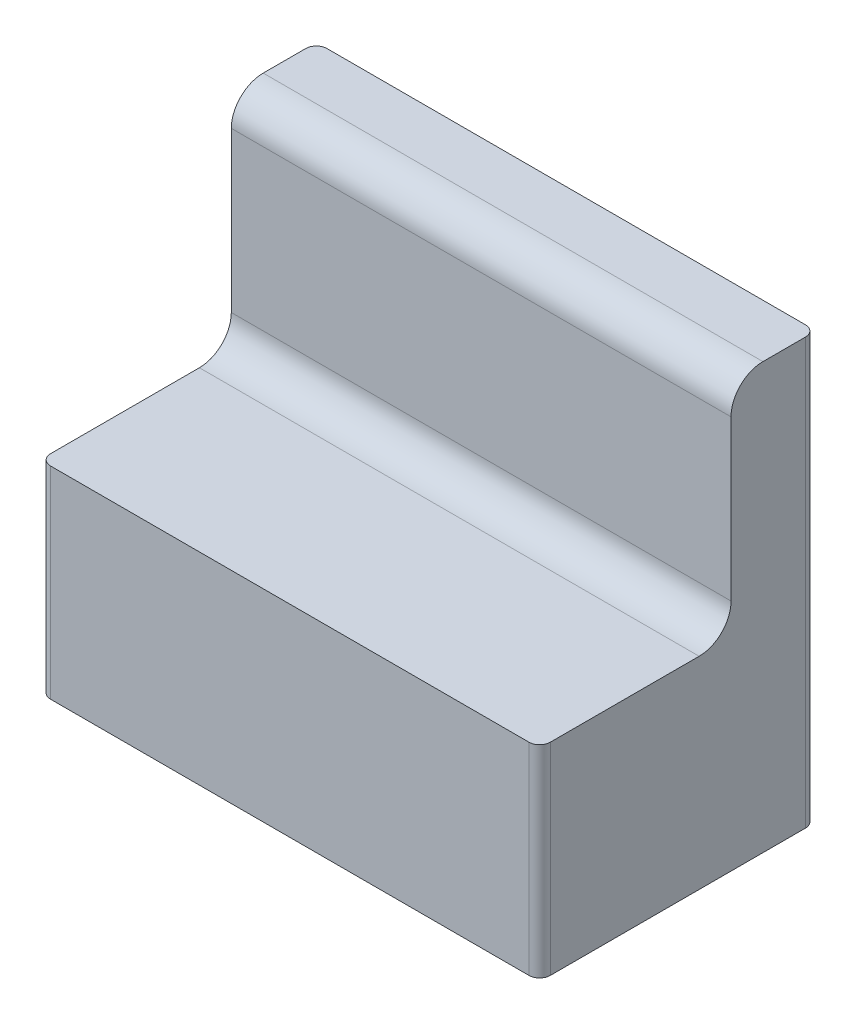
SolidWorks part; units mm, degrees
material "K110"
ref_plane "Front Plane" through (0, 0, 0) normal (0, 0, 1) x (1, 0, 0)
ref_plane "Top Plane" through (0, 0, 0) normal (0, 1, 0) x (1, 0, 0)
ref_plane "Right Plane" through (0, 0, 0) normal (1, 0, 0) x (0, 0, -1)
sketch "Sketch1" plane through (0, 0, 0) normal (0, 1, 0) x (1, 0, 0)
  line L1 (-23.5, -13) -> (23.5, -13)
  line L2 (-23.5, -13) -> (-23.5, 13)
  line L3 (-23.5, 13) -> (23.5, 13)
  line L4 (23.5, -13) -> (23.5, 13)
  line L5 (-23.5, -13) -> (23.5, 13) construction
  line L6 (-23.5, 13) -> (23.5, -13) construction
  point P0 (0, 0)
  dimension "D1" = 26
  dimension "D2" = 47
extrude "Boss-Extrude1" add sketch "Sketch1" against normal blind 40
sketch "Sketch2" plane through (23.5, 0, 0) normal (1, 0, 0) x (0, 0, -1)
  line L0 (13, -40) -> (13, 0) construction
  line L1 (-13, 0) -> (5, 0)
  line L2 (-13, 0) -> (-13, -21)
  line L3 (-13, -21) -> (5, -21)
  line L4 (5, 0) -> (5, -21)
  dimension "D1" = 8
  dimension "D2" = 21
extrude "Cut-Extrude1" cut sketch "Sketch2" against normal up to next
fillet "Fillet1" radius 3 2 edges at (0, 0, -5) (0, -21, -5)
hole_wizard "M6 Tapped Hole1" positions "Sketch6" profile "Sketch4" tap size "M6" standard "ISO"
sketch "Sketch6" plane through (0, -40, 0) normal (0, -1, 0) x (-1, 0, 0)
  line L0 (-23.5, -13) -> (-23.5, 13) construction
  line L1 (23.5, 13) -> (23.5, -13) construction
  point P0 (-15.5, 0)
  point P2 (15.5, 0)
  point P5 (0, 0)
  dimension "D1" = 8
  dimension "D2" = 8
sketch "Sketch4" plane through (15.5, -40, 0) normal (1, 0, 0) x (0, 0, -1)
  line L0 (0, 0) -> (0, 16.5022)
  line L1 (0, 16.5022) -> (2.5, 15)
  line L2 (2.5, 15) -> (2.5, 0.525)
  line L3 (2.5, 0.525) -> (3.025, 0)
  line L5 (3.025, 0) -> (0, 0)
  line L6 (-2.5, 0.525) -> (-3.025, 0) construction
  line L10 (0, 16.5022) -> (-2.5, 15) construction
  line L11 (0, -6.35) -> (0, 107.95) construction
  dimension "Tap Drill Dia." = 5
  dimension "Tap Drill Depth" = 15
  dimension "Near C'Sink Dia." = 6.05
  dimension "Near C'Sink Angle" = 90
  dimension "Drill Angle" = 118
cosmetic thread "Hole Thread1"
cosmetic thread "Hole Thread2"
fillet "Fillet2" radius 1 4 edges at (23.5, -20, -13) (23.5, -30.5, 13) (-23.5, -30.5, 13) (-23.5, -20, -13)
